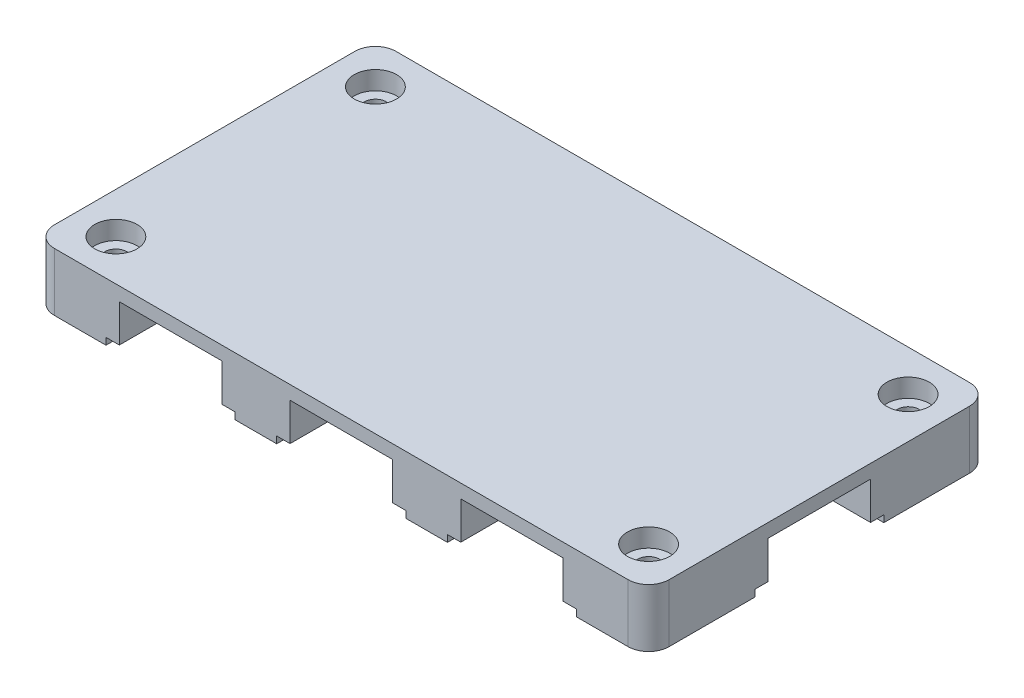
SolidWorks part; units mm, degrees
ref_plane "前视基准面" through (0, 0, 0) normal (0, 0, 1) x (1, 0, 0)
ref_plane "上视基准面" through (0, 0, 0) normal (0, 1, 0) x (1, 0, 0)
ref_plane "右视基准面" through (0, 0, 0) normal (1, 0, 0) x (0, 0, -1)
other "Configuration Table"
sketch "草图1" plane through (0, 0, 0) normal (0, 1, 0) x (1, 0, 0)
  line L1 (-42, -25) -> (42, -25)
  line L2 (-45, -22) -> (-45, 22)
  line L3 (-42, 25) -> (42, 25)
  line L4 (45, -22) -> (45, 22)
  line L5 (-45, -25) -> (45, 25) construction
  line L6 (-45, 25) -> (45, -25) construction
  arc A0 (-42, -25) -> (-45, -22) centre (-42, -22) cw
  arc A1 (45, -22) -> (42, -25) centre (42, -22) cw
  arc A2 (45, 22) -> (42, 25) centre (42, 22) ccw
  arc A3 (-45, 22) -> (-42, 25) centre (-42, 22) cw
  circle A4 centre (-39, 19) radius 1.6
  circle A5 centre (39, 19) radius 1.6
  circle A6 centre (-39, -19) radius 1.6
  circle A7 centre (39, -19) radius 1.6
  point P0 (0, 0)
  dimension "D3" = 3
  dimension "D4" = 3.2
  dimension "D1" = 90
  dimension "D2" = 50
  dimension "D5" = 6
  dimension "D6" = 6
  dimension "D7" = 6
  dimension "D8" = 6
extrude "凸台-拉伸1" add sketch "草图1" along normal blind 8.5
sketch "草图2" plane through (0, 8.5, 0) normal (0, 1, 0) x (1, 0, 0)
  line L0 (0, 31.0621) -> (0, -32.1848) construction
  line L1 (-42, -25) -> (42, -25) construction
  line L2 (-7.5, -14.7) -> (7.5, -14.7)
  line L3 (-7.5, -14.7) -> (-7.5, -25)
  line L4 (-7.5, -25) -> (7.5, -25)
  line L5 (7.5, -14.7) -> (7.5, -25)
  line L6 (-25, 35.1788) -> (-25, -33.1205) construction
  line L7 (0, 0) -> (-45, 0) construction
  line L8 (-45, 22) -> (-45, -22) construction
  line L9 (0, 0) -> (45, 0) construction
  line L10 (-32.5, -14.7) -> (-17.5, -14.7)
  line L11 (-32.5, -14.7) -> (-32.5, -25)
  line L12 (-32.5, -25) -> (-17.5, -25)
  line L13 (-17.5, -14.7) -> (-17.5, -25)
  line L14 (45, -22) -> (45, 22) construction
  line L15 (25, 31.9977) -> (25, -37.05) construction
  line L17 (17.5, -14.7) -> (32.5, -14.7)
  line L18 (17.5, -14.7) -> (17.5, -25)
  line L19 (17.5, -25) -> (32.5, -25)
  line L20 (32.5, -14.7) -> (32.5, -25)
  line L21 (-45, 7.5) -> (-34.7, 7.5)
  line L22 (-45, 7.5) -> (-45, -7.5)
  line L23 (-45, -7.5) -> (-34.7, -7.5)
  line L24 (-34.7, 7.5) -> (-34.7, -7.5)
  line L25 (45, 7.5) -> (34.7, 7.5)
  line L26 (45, 7.5) -> (45, -7.5)
  line L27 (45, -7.5) -> (34.7, -7.5)
  line L28 (34.7, 7.5) -> (34.7, -7.5)
  point P9 (0, -14.7)
  point P21 (-25, -14.7)
  point P32 (25, -14.7)
  point P41 (-34.7, 0)
  point P42 (34.7, 0)
  dimension "D1" = 15
  dimension "D2" = 10.3
  dimension "D3" = 20
  dimension "D4" = 70
sketch "草图3" plane through (0, 8.5, 0) normal (0, 1, 0) x (1, 0, 0)
  line L0 (42, 25) -> (-42, 25) construction
  line L1 (-13.742, 25) -> (-4.542, 25)
  line L2 (-13.742, 25) -> (-13.742, 17.4)
  line L3 (-13.742, 17.4) -> (-4.542, 17.4)
  line L4 (-4.542, 25) -> (-4.542, 17.4)
  line L5 (-9.142, 32.9169) -> (-9.142, 4.8795) construction
  line L6 (-45, 22) -> (-45, -22) construction
  point P10 (-9.142, 17.4)
  dimension "D1" = 9.2
  dimension "D2" = 7.6
  dimension "D3" = 35.858
sketch "草图4" plane through (0, 8.5, 0) normal (0, 1, 0) x (1, 0, 0)
  line L0 (6.466, 34.8045) -> (6.466, -37.05) construction
  line L1 (-45, 22) -> (-45, -22) construction
  line L2 (42, 25) -> (-42, 25) construction
  line L3 (2.466, 25) -> (10.466, 25)
  line L4 (2.466, 25) -> (2.466, 19)
  line L5 (2.466, 19) -> (10.466, 19)
  line L6 (10.466, 25) -> (10.466, 19)
  point P10 (6.466, 19)
  dimension "D1" = 51.466
  dimension "D2" = 6
  dimension "D3" = 8
sketch "草图7" plane through (0, 8.5, 0) normal (0, 1, 0) x (1, 0, 0)
  line L0 (-25, 40.2318) -> (-25, -33.5875) construction
  line L1 (-29.8, 21.9) -> (-20.2, 21.9)
  line L2 (-29.8, 21.9) -> (-29.8, 33)
  line L3 (-29.8, 33) -> (-20.2, 33)
  line L4 (-20.2, 21.9) -> (-20.2, 33)
  line L5 (-45, 22) -> (-45, -22) construction
  line L6 (42, 25) -> (-42, 25) construction
  point P8 (-25, 21.9)
  dimension "D1" = 20
  dimension "D2" = 9.6
  dimension "D3" = 3.1
  dimension "D4" = 11.1
extrude "切除-拉伸1" cut sketch "草图2" along normal blind 6.5 from surface starting at face at (-39, 0, 20.6)
extrude "切除-拉伸2" cut sketch "草图3" along normal blind 3.4 from surface starting at face at (0, 0, 8.5071)
extrude "切除-拉伸3" cut sketch "草图4" along normal blind 2.6 from surface starting at face at (-1.1427, 0, 4.7938)
extrude "切除-拉伸4" cut sketch "草图7" along normal blind 1 from surface starting at face at (-0.2973, 0, 1.8167)
sketch "草图8" plane through (0, 0, 0) normal (0, -1, 0) x (1, 0, 0)
  line L0 (-25, 33.8928) -> (-25, -41.0205) construction
  line L1 (-33.2, -9.45) -> (-45, -9.45)
  line L2 (-33.2, -9.45) -> (-33.2, 9.45)
  line L3 (-33.2, 9.45) -> (-45, 9.45)
  line L4 (-45, -9.45) -> (-45, 9.45)
  line L7 (-31.5, -1) -> (-27.3, -1)
  line L8 (-31.5, -1) -> (-31.5, 1)
  line L9 (-31.5, 1) -> (-27.3, 1)
  line L10 (-27.3, -1) -> (-27.3, 1)
  line L11 (-29.15, -20.5) -> (-20.85, -20.5)
  line L12 (-29.15, -20.5) -> (-29.15, -21.9)
  line L13 (-29.15, -21.9) -> (-20.85, -21.9)
  line L14 (-20.85, -20.5) -> (-20.85, -21.9)
  line L15 (-17.66, -19.4) -> (-16.46, -19.4)
  line L16 (-17.66, -19.4) -> (-17.66, -17.4)
  line L17 (-17.66, -17.4) -> (-16.46, -17.4)
  line L18 (-16.46, -19.4) -> (-16.46, -17.4)
  line L19 (-0.712, -19.4) -> (-1.912, -19.4)
  line L20 (-0.712, -19.4) -> (-0.712, -17.4)
  line L21 (-0.712, -17.4) -> (-1.912, -17.4)
  line L22 (-1.912, -19.4) -> (-1.912, -17.4)
  line L23 (4.766, -19) -> (8.166, -19)
  line L24 (4.766, -19) -> (4.766, -17.6)
  line L25 (4.766, -17.6) -> (8.166, -17.6)
  line L26 (8.166, -19) -> (8.166, -17.6)
  line L27 (18.85, -19.3) -> (31.15, -19.3)
  line L28 (18.85, -19.3) -> (18.85, -25)
  line L29 (18.85, -25) -> (31.15, -25)
  line L30 (31.15, -19.3) -> (31.15, -25)
  line L31 (-45, 7.5) -> (-45, 22) construction
  line L32 (-17.5, 25) -> (-32.5, 25) construction
  line L33 (20, -6.4) -> (34.7, -6.4)
  line L34 (20, -6.4) -> (20, 6.4)
  line L35 (20, 6.4) -> (34.7, 6.4)
  line L36 (34.7, -6.4) -> (34.7, 6.4)
  line L37 (33.2, -9.45) -> (45, -9.45)
  line L38 (33.2, -9.45) -> (33.2, 9.45)
  line L39 (33.2, 9.45) -> (45, 9.45)
  line L40 (45, -9.45) -> (45, 9.45)
  line L41 (25, 37.9856) -> (25, 9.6) construction
  line L42 (7.5, 25) -> (17.5, 25) construction
  line L43 (-34.45, 13.2) -> (-15.55, 13.2)
  line L44 (-34.45, 13.2) -> (-34.45, 25)
  line L45 (-34.45, 25) -> (-15.55, 25)
  line L46 (-15.55, 13.2) -> (-15.55, 25)
  line L49 (-9.45, 13.2) -> (9.45, 13.2)
  line L50 (-9.45, 13.2) -> (-9.45, 25)
  line L51 (-9.45, 25) -> (9.45, 25)
  line L52 (9.45, 13.2) -> (9.45, 25)
  line L54 (15.55, 13.2) -> (34.45, 13.2)
  line L55 (15.55, 13.2) -> (15.55, 25)
  line L56 (15.55, 25) -> (34.45, 25)
  line L57 (34.45, 13.2) -> (34.45, 25)
  point P6 (-25, 13.2)
  point P25 (25, 13.2)
  dimension "D1" = 18.9
  dimension "D2" = 20
  dimension "D3" = 11.8
  dimension "D4" = 70
extrude "切除-拉伸5" cut sketch "草图8" against normal blind 3.4 contours L27 L30 L29 L28
extrude "切除-拉伸6" cut sketch "草图8<3>" against normal blind 2 contours L33 L36 L35 L34
sketch "草图8<3>" plane through (0, 0, 0) normal (0, -1, 0) x (1, 0, 0) same geometry as "草图8"
extrude "切除-拉伸7" cut sketch "草图8<4>" against normal blind 1 contours L39 L40 L37 L38 | L25 L26 L23 L24 | L22 L21 L20 L19 | L16 L17 L18 L15 | L11 L14 L13 L12 | L9 L10 L7 L8 | L2 L3 L4 L1 | L43 L46 L45 L44 | L49 L52 L51 L50 | L54 L57 L56 L55
sketch "草图8<4>" plane through (0, 0, 0) normal (0, -1, 0) x (1, 0, 0) same geometry as "草图8"
sketch "草图9" plane through (0, 8.5, 0) normal (0, 1, 0) x (1, 0, 0)
  circle A0 centre (-39, 19) radius 3.1
  circle A1 centre (-39, -19) radius 3.1
  circle A2 centre (39, 19) radius 3.1
  circle A3 centre (39, -19) radius 3.1
  dimension "D1" = 6.2
extrude "切除-拉伸8" cut sketch "草图9" against normal blind 2.7 contours A0 | A1 | A3 | A2
